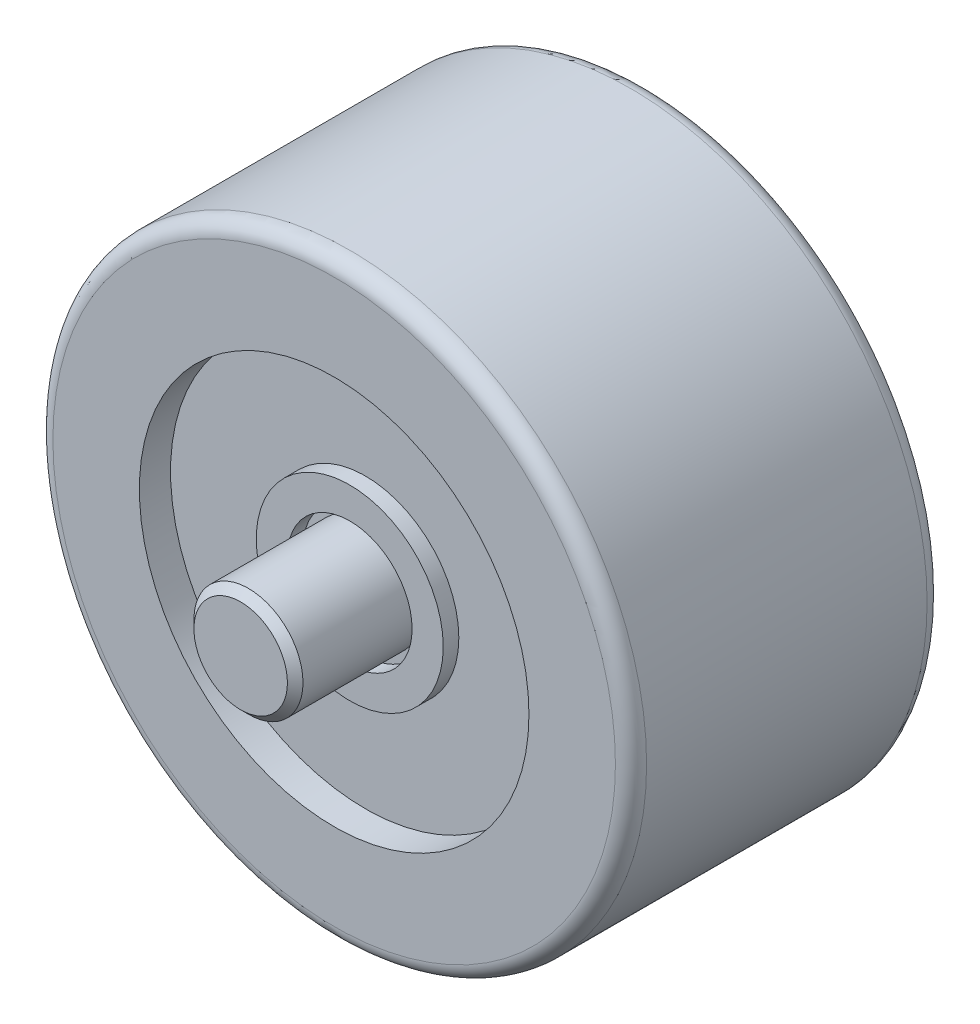
SolidWorks part; units mm, degrees
ref_plane "Front Plane" through (0, 0, 0) normal (0, 0, 1) x (1, 0, 0)
ref_plane "Top Plane" through (0, 0, 0) normal (0, 1, 0) x (1, 0, 0)
ref_plane "Right Plane" through (0, 0, 0) normal (1, 0, 0) x (0, 0, -1)
sketch "Sketch1" plane through (0, 0, 0) normal (0, 0, 1) x (1, 0, 0)
  circle A0 centre (0, 0) radius 19.05
  dimension "D1" = 38.1
extrude "Boss-Extrude1" add sketch "Sketch1" along normal blind 10 and the other way blind 10
fillet "Fillet1" radius 1 2 edges at (19.05, 0, -10) (19.05, 0, 10)
sketch "Sketch2" plane through (0, 0, 10) normal (0, 0, 1) x (1, 0, 0)
  circle A0 centre (0, 0) radius 12.5
  dimension "D1" = 25
extrude "Cut-Extrude1" cut sketch "Sketch2" against normal blind 2
sketch "Sketch3" plane through (0, 0, -10) normal (0, 0, -1) x (-1, 0, 0)
  circle A0 centre (0, 0) radius 12.5
  circle A1 centre (0, 0) radius 12.5 construction
extrude "Cut-Extrude2" cut sketch "Sketch3" against normal blind 2
sketch "Sketch4" plane through (0, 0, 8) normal (0, 0, 1) x (1, 0, 0)
  circle A0 centre (0, 0) radius 6
  circle A1 centre (0, 0) radius 4
  dimension "D1" = 12
  dimension "D2" = 8
extrude "Boss-Extrude2" add sketch "Sketch4" along normal blind 1
mirror "Mirror1" about plane through (0, 0, 0) normal (0, 0, 1) of "Boss-Extrude2"
sketch "Sketch5" plane through (0, 0, 8) normal (0, 0, 1) x (1, 0, 0)
  circle A1 centre (0, 0) radius 3.5
  circle A2 centre (0, 0) radius 4 construction
  dimension "D1" = 0.5
extrude "Boss-Extrude3" add sketch "Sketch5" along normal blind 8
mirror "Mirror2" about plane through (0, 0, 0) normal (0, 0, 1) of "Boss-Extrude3"
chamfer "Chamfer1" distance 0.5 angle 45 2 edges at (3.5, 0, -16) (3.5, 0, 16)
